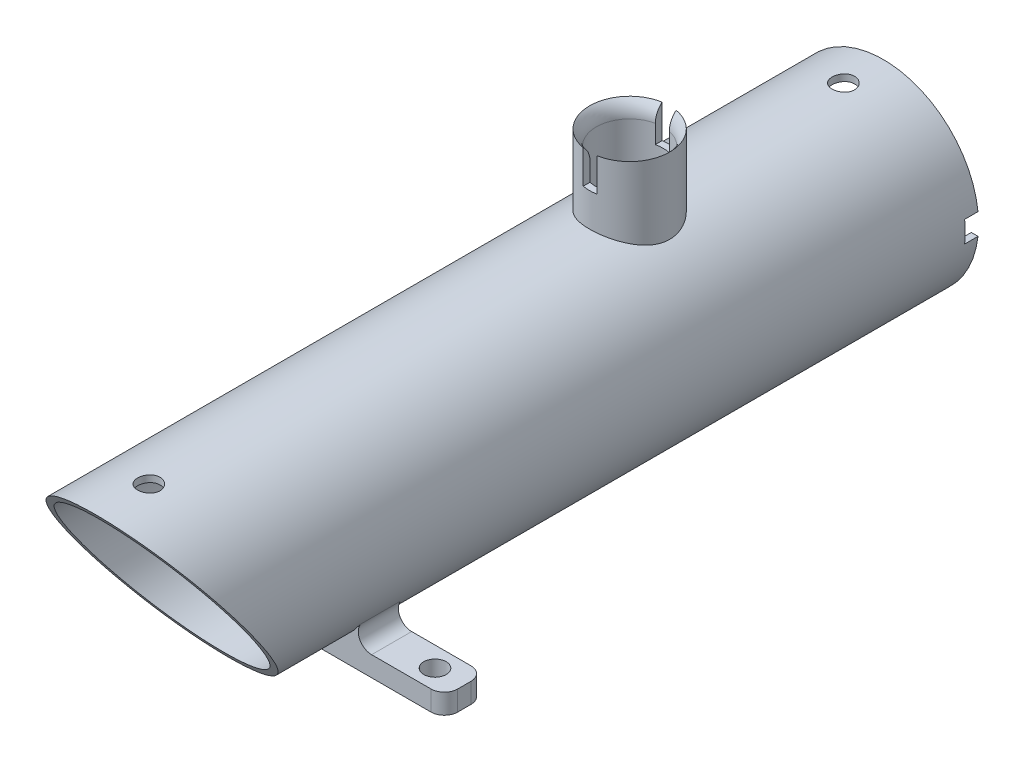
SolidWorks part; units mm, degrees
ref_plane "Front Plane" through (0, 0, 0) normal (0, 0, 1) x (1, 0, 0)
ref_plane "Top Plane" through (0, 0, 0) normal (0, 1, 0) x (1, 0, 0)
ref_plane "Right Plane" through (0, 0, 0) normal (1, 0, 0) x (0, 0, -1)
sketch "Sketch4" plane through (0, 0, 0) normal (0, 0, 1) x (1, 0, 0)
  circle A0 centre (0, 0) radius 14.25
  circle A1 centre (0, 0) radius 13.25
  dimension "D1" = 26.5
  dimension "D2" = 1
extrude "Boss-Extrude3" add sketch "Sketch4" along normal blind 118
sketch "Sketch5" plane through (0, 0, 118) normal (0, 0, 1) x (1, 0, 0)
  circle A0 centre (0, 0) radius 14.25 construction
  point P0 (0, 14.25)
  point P1 (14.25, 0)
  point P4 (-14.25, 0)
  point P5 (0, -14.25)
ref_plane "Plane1" through (0, 14.25, 118) normal (0, 1, 0) x (1, 0, 0)
sketch "Sketch6" plane through (0, 14.25, 118) normal (0, 1, 0) x (1, 0, 0)
  line L0 (-14.25, 0) -> (14.25, 0) construction
  circle A0 centre (0, 80) radius 5
  circle A1 centre (0, 80) radius 6
  dimension "D1" = 10
  dimension "D2" = 1
  dimension "D3" = 80
extrude "Boss-Extrude4" add sketch "Sketch6" along normal blind 10 and the other way blind 4
sketch "Sketch7" plane through (0, 24.25, 0) normal (0, 1, 0) x (1, 0, 0)
  circle A0 centre (0, -38) radius 5
  circle A1 centre (0, -38) radius 5 construction
extrude "Cut-Extrude1" cut sketch "Sketch7" against normal blind 20
sketch "Sketch8" plane through (0, 0, 118) normal (0, 0, 1) x (1, 0, 0)
  circle A0 centre (0, 0) radius 13.25
extrude "Cut-Extrude2" cut sketch "Sketch8" against normal up to surface (118 mm away) up to face at (14.25, 0, 0)
sketch "Sketch11" plane through (0, 14.25, 118) normal (0, 1, 0) x (1, 0, 0)
  line L0 (-14.25, 0) -> (14.25, 0) construction
  line L1 (13.25, 118) -> (-13.25, 118) construction
  circle A0 centre (0, 8) radius 1.675
  circle A1 centre (0, 112) radius 1.675
  dimension "D1" = 3.35
  dimension "D2" = 8
  dimension "D3" = 6
extrude "Cut-Extrude5" cut sketch "Sketch11" against normal blind 13
ref_plane "Plane5" through (0, -14.25, 118) normal (0, -1, 0) x (-1, 0, 0)
sketch "Sketch15" plane through (0, -14.25, 118) normal (0, -1, 0) x (-1, 0, 0)
  line L5 (0, 65) -> (0, 0) construction
  line L7 (0, 28) -> (-24.25, 28)
  line L13 (0, 28) -> (0, 34)
  line L14 (0, 34) -> (-24.25, 34)
  line L15 (-24.25, 28) -> (-24.25, 34)
  line L16 (-14.25, 118) -> (-14.25, 0) construction
  line L17 (-14.25, 0) -> (14.25, 0) construction
  line L18 (-24.25, 31) -> (0, 31) construction
  circle A2 centre (-19.85, 31) radius 1.675
  point P0 (0, 65)
  point P15 (0, 65)
  point P16 (0, 22.5)
  dimension "D4" = 3.35
  dimension "D6" = 5.6
  dimension "D1" = 10
  dimension "D2" = 6
  dimension "D3" = 28
fillet "Fillet2" radius 3 1 edges at (-5, 24.25, 38)
sketch "Sketch20" plane through (0, 14.25, 118) normal (0, 1, 0) x (1, 0, 0)
  line L1 (-1.05, 86) -> (1.05, 86)
  line L2 (-1.05, 86) -> (-1.05, 83)
  line L3 (-1.05, 83) -> (1.05, 83)
  line L4 (1.05, 86) -> (1.05, 83)
  line L5 (-1.05, 77) -> (1.05, 77)
  line L6 (-1.05, 77) -> (-1.05, 74)
  line L7 (-1.05, 74) -> (1.05, 74)
  line L8 (1.05, 77) -> (1.05, 74)
  circle A2 centre (0, 80) radius 6 construction
  circle A3 centre (0, 80) radius 4.7474
  circle A4 centre (0, 80) radius 5 construction
  point P14 (0, 77)
  point P15 (0, 83)
  dimension "D1" = 2.1
  dimension "D2" = 3
extrude "Boss-Extrude8" add sketch "Sketch15" against normal blind 3
sketch "Sketch27" plane through (0, 0, 0) normal (0, 0, -1) x (-1, 0, 0)
  circle A0 centre (0, 0) radius 13.25
extrude "Cut-Extrude15" cut sketch "Sketch27" against normal up to surface (118 mm away) up to face at (14.25, 0, 118)
sketch "Sketch29" plane through (0, 0, 0) normal (0, 0, -1) x (-1, 0, 0)
  line L1 (-17.6299, -1.6) -> (17.6299, -1.6)
  line L2 (-17.6299, -1.6) -> (-17.6299, 1.6)
  line L3 (-17.6299, 1.6) -> (17.6299, 1.6)
  line L4 (17.6299, -1.6) -> (17.6299, 1.6)
  line L5 (-17.6299, -1.6) -> (17.6299, 1.6) construction
  line L6 (-17.6299, 1.6) -> (17.6299, -1.6) construction
  point P0 (0, 0)
  dimension "D1" = 3.2
extrude "Cut-Extrude17" cut sketch "Sketch29" against normal blind 2
extrude "Cut-Extrude18" cut sketch "Sketch20" along normal blind 10 from offset 5 contours A3 L4 L1 L2 | A3 L6 L7 L8 region at (0, 14.25, 32.6463) region at (0, 14.25, 43.3537)
sketch "Sketch30" plane through (24.25, 0, 0) normal (1, 0, 0) x (0, 0, -1)
  line L0 (-118, 14.25) -> (-98.0441, -14.25)
  line L1 (-118, -14.25) -> (-90, -14.25) construction
  line L2 (-98.0441, -14.25) -> (-118, -14.25)
  line L3 (-118, -14.25) -> (-118, 14.25)
  dimension "D1" = 35
extrude "Cut-Extrude19" cut sketch "Sketch30" against normal blind 50
fillet "Fillet3" radius 2 3 edges at (8.7464, -11.25, 87) (24.25, -12.75, 90) (24.25, -12.75, 84)
